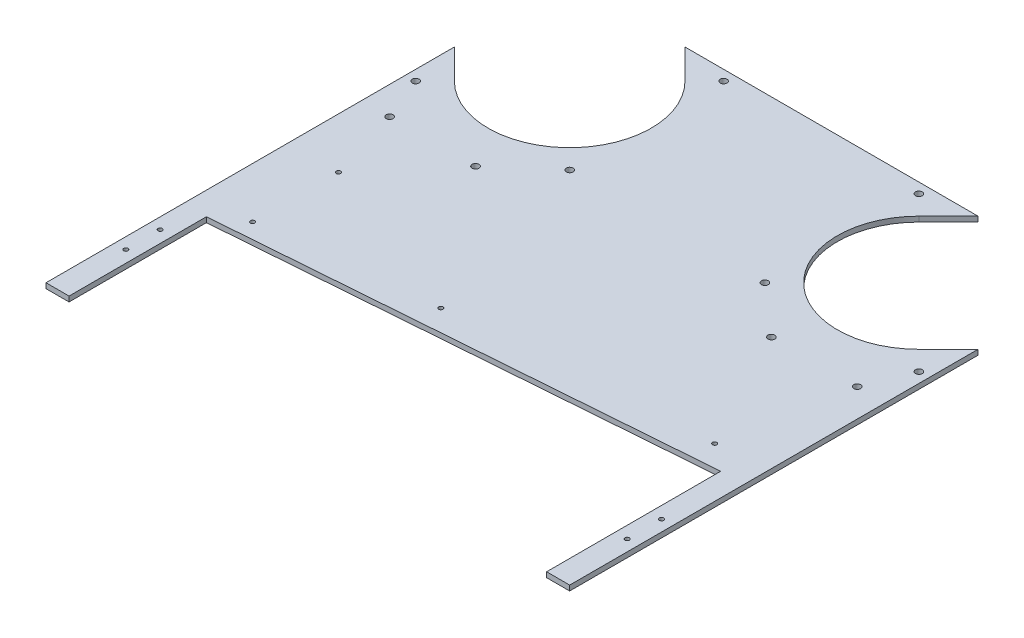
SolidWorks part; units mm, degrees
material "6061 Alloy"
ref_plane "Front Plane" through (0, 0, 0) normal (0, 0, 1) x (1, 0, 0)
ref_plane "Top Plane" through (0, 0, 0) normal (0, 1, 0) x (1, 0, 0)
ref_plane "Right Plane" through (0, 0, 0) normal (1, 0, 0) x (0, 0, -1)
sketch "Sketch1" plane through (0, 0, 0) normal (0, 1, 0) x (1, 0, 0)
  line L0 (0, 0) -> (0, 200)
  line L1 (0, 200) -> (305, 200)
  line L2 (305, 200) -> (305, 35.3098)
  line L3 (291.5711, -3.6044) -> (13.4289, -25)
  line L4 (0, 0) -> (0, -105)
  line L5 (0, -105) -> (13.4289, -105)
  line L6 (13.4289, -105) -> (13.4289, -25)
  line L7 (305, 35.3098) -> (305, -105)
  line L8 (305, -105) -> (291.5711, -105)
  line L9 (291.5711, -105) -> (291.5711, -3.6044)
  dimension "D1" = 305
  dimension "D2" = 85.601
  dimension "D3" = 200
  dimension "D4" = 13.4289
  dimension "D5" = 13.4289
  dimension "D6" = 105
  dimension "D7" = 305
  dimension "D8" = 80
sheet metal parameters "Sheet-Metal1" thickness 3 parameters "D1"=0.7366
base flange "Base-Flange1" sketch "Sketch1" thickness 3 reverse thickness direction no parameters "D1"=0.7366
hole_wizard "M3 Tapped Hole1" positions "Sketch6" profile "Sketch5" tap size "M3" standard "ISO"
sketch "Sketch6" plane through (0, 0, 0) normal (0, 1, 0) x (1, 0, 0)
  line L0 (0, 200) -> (0, -105) construction
  line L1 (305, -105) -> (305, 200) construction
  line L2 (0, -105) -> (13.4289, -105) construction
  line L3 (291.5711, -105) -> (305, -105) construction
  point P0 (6.5, -45)
  point P2 (6.5, -65)
  point P4 (298.5, -45)
  point P6 (298.5, -65)
  dimension "D1" = 6.5
  dimension "D3" = 6.5
  dimension "D5" = 20
  dimension "D6" = 20
  dimension "D7" = 40
  dimension "D8" = 40
sketch "Sketch5" plane through (6.5, 0, 45) normal (1, 0, 0) x (0, 0, 1)
  line L0 (0, 0) -> (0, 8.2511)
  line L1 (0, 8.2511) -> (1.25, 7.5)
  line L2 (1.25, 7.5) -> (1.25, 0)
  line L5 (1.25, 0) -> (0, 0)
  line L10 (0, 8.2511) -> (-1.25, 7.5) construction
  line L11 (0, -6.35) -> (0, 107.95) construction
  dimension "Tap Drill Dia." = 2.5
  dimension "Tap Drill Depth" = 7.5
  dimension "Drill Angle" = 118
cosmetic thread "Hole Thread1" parameters "D1"=3, "D2"=3
cosmetic thread "Hole Thread2" parameters "D1"=3, "D2"=3
cosmetic thread "Hole Thread3" parameters "D1"=3, "D2"=3
cosmetic thread "Hole Thread4" parameters "D1"=3, "D2"=3
hole_wizard "M3 Tapped Hole2" positions "Sketch10" profile "Sketch9" tap size "M3" standard "ISO"
sketch "Sketch10" plane through (0, 0, 0) normal (0, 1, 0) x (1, 0, 0)
  point P3 (127.7449, -2.7987)
  point P6 (275.8299, 8.5925)
sketch "Sketch9" plane through (127.7449, 0, 2.7987) normal (1, 0, 0) x (0, 0, 1)
  line L0 (0, 0) -> (0, 8.2511)
  line L1 (0, 8.2511) -> (1.25, 7.5)
  line L2 (1.25, 7.5) -> (1.25, 0)
  line L5 (1.25, 0) -> (0, 0)
  line L10 (0, 8.2511) -> (-1.25, 7.5) construction
  line L11 (0, -6.35) -> (0, 107.95) construction
  dimension "Tap Drill Dia." = 2.5
  dimension "Tap Drill Depth" = 7.5
  dimension "Drill Angle" = 118
cosmetic thread "Hole Thread5" parameters "D1"=3, "D2"=3
cosmetic thread "Hole Thread6" parameters "D1"=3, "D2"=3
sketch "Sketch11" plane through (0, 0, 0) normal (0, 1, 0) x (1, 0, 0)
  line L0 (0, 132.8249) -> (17.2124, 115.6124)
  line L1 (0, 200) -> (0, -105) construction
  line L2 (17.2124, 115.6124) -> (0, 115.6124) construction
  line L3 (84.3876, 182.7876) -> (67.1751, 200)
  line L4 (305, 200) -> (0, 200) construction
  line L5 (220.6124, 182.7876) -> (237.8249, 200)
  line L6 (287.7876, 115.6124) -> (305, 132.8249)
  line L7 (305, -105) -> (305, 200) construction
  line L8 (287.7876, 115.6124) -> (305, 115.6124) construction
  line L9 (0, 132.8249) -> (0, 200)
  line L10 (0, 200) -> (67.1751, 200)
  circle A0 centre (50.8, 149.2) radius 47.5
  circle A1 centre (254.2, 149.2) radius 47.5
  circle A2 centre (95.6437, 194.0437) radius 1.9844
  circle A3 centre (5.9563, 104.3563) radius 1.9844
  circle A4 centre (95.6437, 104.3563) radius 1.9844
  circle A5 centre (209.3563, 104.3563) radius 1.9844
  circle A6 centre (299.0437, 104.3563) radius 1.9844
  circle A7 centre (209.3563, 194.0437) radius 1.9844
  circle A8 centre (66.3384, 78.8315) radius 2
  circle A9 centre (16.3384, 78.8315) radius 2
  circle A10 centre (288.6616, 78.8319) radius 2
  circle A11 centre (238.6616, 78.8319) radius 2
  line M10 (0, 200) -> (0, -105)
  line M16 (305, -105) -> (305, 200)
  line M17 (305, 200) -> (0, 200)
  dimension "D2" = 95
  dimension "D3" = 95
  dimension "D8" = 3.9688
  dimension "D9" = 3.9688
  dimension "D11" = 3.9688
  dimension "D15" = 3.9687
  dimension "D16" = 3.9687
  dimension "D19" = 3.9687
  dimension "D18" = 4
  dimension "D20" = 4
  dimension "D21" = 4
  dimension "D22" = 4
  dimension "D1" = 45
  dimension "D4" = 45
  dimension "D5" = 5.9563
  dimension "D6" = 89.6874
  dimension "D7" = 95.6437
  dimension "D10" = 5.9563
  dimension "D12" = 5.9563
  dimension "D13" = 95.6437
  dimension "D14" = 95.6437
  dimension "D17" = 5.9563
extrude "Cut-Extrude1" cut sketch "Sketch11" against normal through all contours A0 L3 L0 M17 M10 | A0 | A1 | A1 L6 L5 M16 M17 | A2 | A3 | A4 | A7 | A5 | A6 | A9 | A8 | A11 | A10 region at (1.1934, 0, -166.4124) region at (271.4124, 0, -198.8066) region at (50.8, 0, -149.2) region at (254.2, 0, -149.2) region at (95.6437, 0, -194.0437) region at (5.9563, 0, -104.3563) region at (95.6437, 0, -104.3563) region at (209.3563, 0, -104.3563) region at (299.0437, 0, -104.3563) region at (209.3563, 0, -194.0437) region at (66.3384, 0, -78.8315) region at (16.3384, 0, -78.8315) region at (288.6616, 0, -78.8319) region at (238.6616, 0, -78.8319) normal cut yes
hole_wizard "M3 Tapped Hole3" positions "Sketch13" profile "Sketch12" tap size "M3" standard "ISO"
sketch "Sketch13" plane through (0, 0, 0) normal (0, 1, 0) x (1, 0, 0)
  point P0 (29.4743, 35.8573)
  point P3 (29.4743, -14.1427)
sketch "Sketch12" plane through (29.4743, 0, -35.8573) normal (1, 0, 0) x (0, 0, 1)
  line L0 (0, 0) -> (0, 8.2511)
  line L1 (0, 8.2511) -> (1.25, 7.5)
  line L2 (1.25, 7.5) -> (1.25, 0)
  line L5 (1.25, 0) -> (0, 0)
  line L10 (0, 8.2511) -> (-1.25, 7.5) construction
  line L11 (0, -6.35) -> (0, 107.95) construction
  dimension "Tap Drill Dia." = 2.5
  dimension "Tap Drill Depth" = 7.5
  dimension "Drill Angle" = 118
cosmetic thread "Hole Thread7" parameters "D1"=3, "D2"=3
cosmetic thread "Hole Thread8" parameters "D1"=3, "D2"=3
flat pattern "Flat-Pattern1" [suppressed]
sketch "Bend-Lines1" plane through (0, 0, 0) normal (0, 1, 0) x (1, 0, 0)
sketch3d "Bounding-Box1" [suppressed]
  line L0 (-304.8, 200, 0) -> (0, 200, 0) construction
  line L1 (-304.8, 0, 0) -> (0, 0, 0) construction
  line L2 (-304.8, 200, 0) -> (-304.8, 0, 0) construction
  line L3 (0, 200, 0) -> (0, 0, 0) construction
equation "\"D5@Sketch1\"=\"D4@Sketch1\""
